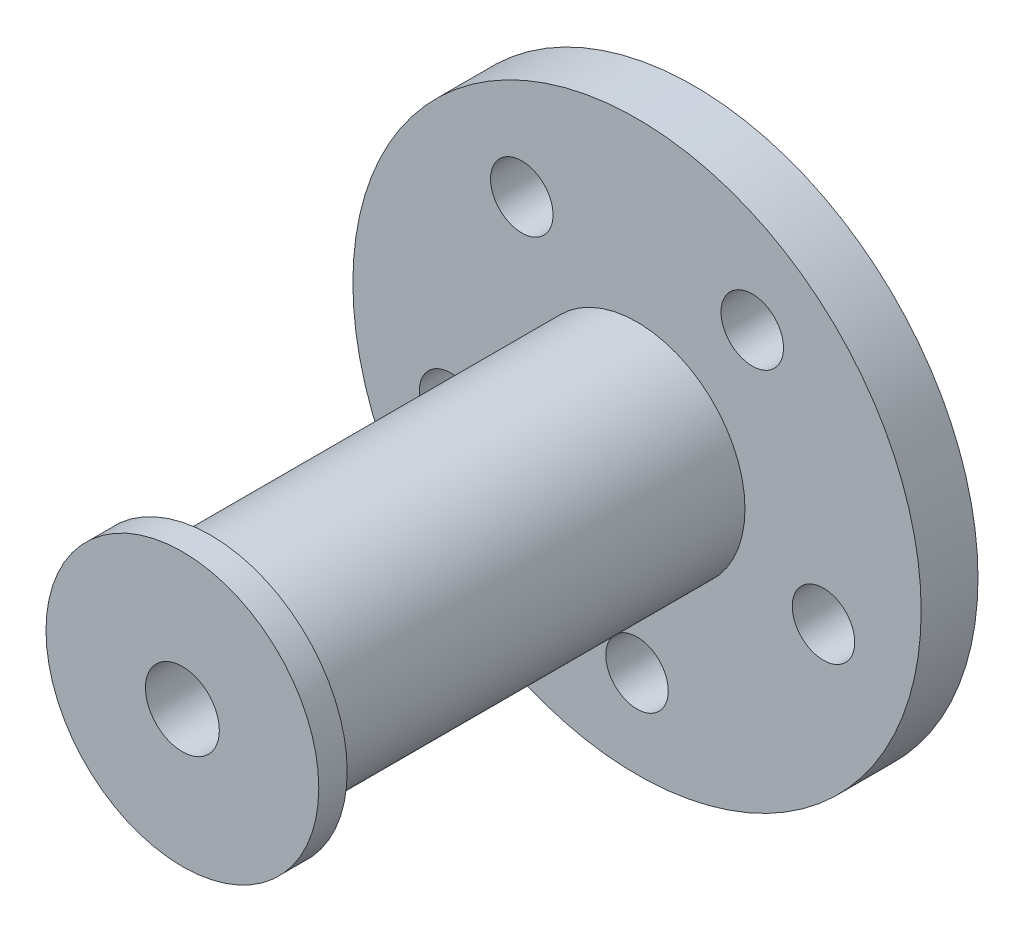
SolidWorks part; units mm, degrees
ref_plane "Front Plane" through (0, 0, 0) normal (0, 0, 1) x (1, 0, 0)
ref_plane "Top Plane" through (0, 0, 0) normal (0, 1, 0) x (1, 0, 0)
ref_plane "Right Plane" through (0, 0, 0) normal (1, 0, 0) x (0, 0, -1)
sketch "Sketch1" plane through (0, 0, 0) normal (0, 0, 1) x (1, 0, 0)
  circle A0 centre (0, 0) radius 31.75
  dimension "D1" = 63.5
extrude "Boss-Extrude1" add sketch "Sketch1" along normal blind 6.35
sketch "Sketch2" plane through (0, 0, 6.35) normal (0, 0, 1) x (1, 0, 0)
  circle A0 centre (0, 0) radius 12.065
  dimension "D1" = 24.13
extrude "Boss-Extrude2" add sketch "Sketch2" along normal blind 50.8
ref_plane "Plane1" through (0, 0, 57.15) normal (0, 0, 1) x (1, 0, 0)
sketch "Sketch4" plane through (0, 0, 57.15) normal (0, 0, 1) x (1, 0, 0)
  circle A0 centre (0, 0) radius 15.24
  circle A1 centre (0, 0) radius 12.065
  circle A2 centre (0, 0) radius 12.065
  dimension "D1" = 0
  dimension "D2" = 3.175
extrude "Boss-Extrude3" add sketch "Sketch4" against normal blind 3.175
sketch "Sketch5" plane through (0, 0, 6.35) normal (0, 0, 1) x (1, 0, 0)
  line L0 (0, -12.065) -> (0, -31.75)
  circle A0 centre (0, -21.9075) radius 3.4925
  circle A1 centre (0, 0) radius 12.065 construction
  circle A2 centre (0, 0) radius 31.75 construction
  point P2 (0, 0)
  dimension "D1" = 6.985
extrude "Cut-Extrude1" cut sketch "Sketch5" against normal through all contours L0 A0 | L0 A0 region at (1.4823, -21.9075, 6.35) region at (-1.4823, -21.9075, 6.35)
pattern_circular "CirPattern1" count 5 over 360 about axis through (0, 0, 6.35) along (0, 0, 1) of "Cut-Extrude1"
sketch "Sketch6" plane through (0, 0, 57.15) normal (0, 0, 1) x (1, 0, 0)
  circle A0 centre (0, 0) radius 3.048
  circle A1 centre (0, 0) radius 4.1275
  dimension "D1" = 6.096
  dimension "D2" = 8.255
extrude "Cut-Extrude2" cut sketch "Sketch6" against normal through all contours A0 region at (0, 0, 57.15)
extrude "Cut-Extrude3" cut sketch "Sketch6<3>" against normal blind 55.499
sketch "Sketch6<3>" plane through (0, 0, 57.15) normal (0, 0, 1) x (1, 0, 0) same geometry as "Sketch6"
